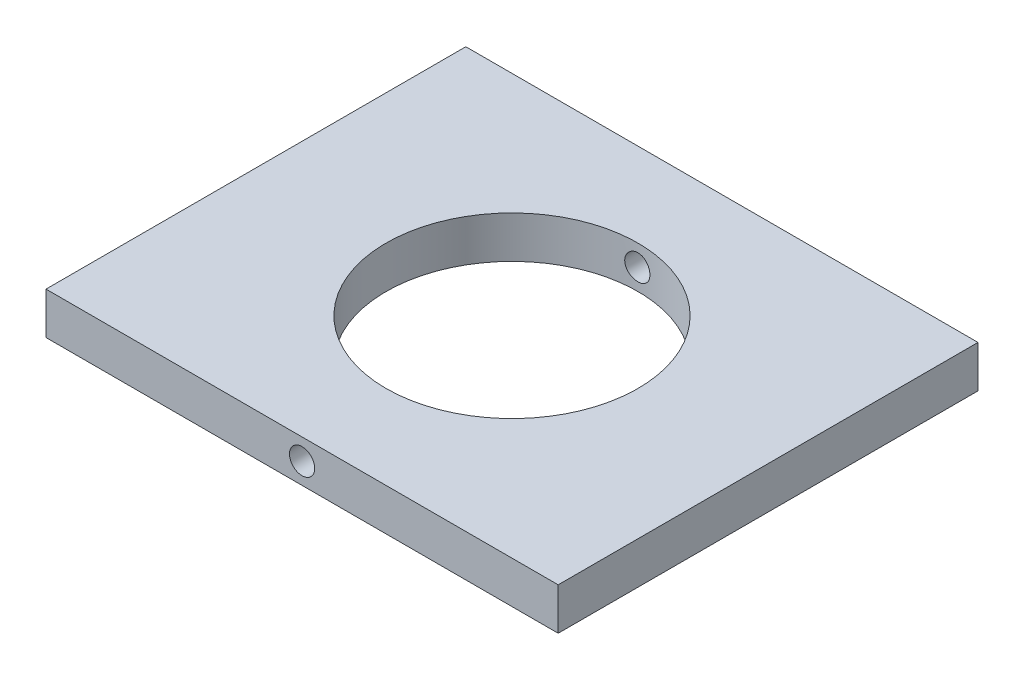
SolidWorks part; units mm, degrees
ref_plane "Plan de face" through (0, 0, 0) normal (0, 0, 1) x (1, 0, 0)
ref_plane "Plan de dessus" through (0, 0, 0) normal (0, 1, 0) x (1, 0, 0)
ref_plane "Plan de droite" through (0, 0, 0) normal (1, 0, 0) x (0, 0, -1)
sketch "Esquisse1" plane through (0, 0, 0) normal (0, 0, 1) x (1, 0, 0)
  line L0 (-8.5, -47.5) -> (52.5, -47.5) construction
  line L5 (-8.5, -45) -> (52.5, -45)
  line L6 (-8.5, -45) -> (-8.5, -50)
  line L7 (-8.5, -50) -> (52.5, -50)
  line L8 (52.5, -45) -> (52.5, -50)
  line L9 (22, -45) -> (22, -50) construction
  dimension "D1" = 5
  dimension "D2" = 61
extrude "Boss.-Extru.1" add sketch "Esquisse1" along normal blind 50 contours L5 | L7 L8 L5 L6
sketch "Esquisse2" plane through (0, -45, 0) normal (0, 1, 0) x (-1, 0, 0)
  line L0 (8.5, 50) -> (-52.5, 50) construction
  line L7 (-52.5, 50) -> (-52.5, 0) construction
  circle A0 centre (-22, 25) radius 15
  dimension "D10" = 30.5
  dimension "D11" = 25
extrude "Enlèv. mat.-Extru.1" cut sketch "Esquisse2" against normal through all
sketch "Esquisse5" plane through (0, 0, 50) normal (0, 0, 1) x (1, 0, 0)
  line L0 (-8.5, -45) -> (52.5, -45) construction
  line L1 (-8.5, -45) -> (-8.5, -50) construction
  circle A0 centre (22, -47.5) radius 1.5
  dimension "D1" = 2.5
  dimension "D2" = 30.5
extrude "Enlèv. mat.-Extru.4" cut sketch "Esquisse5" against normal through all
